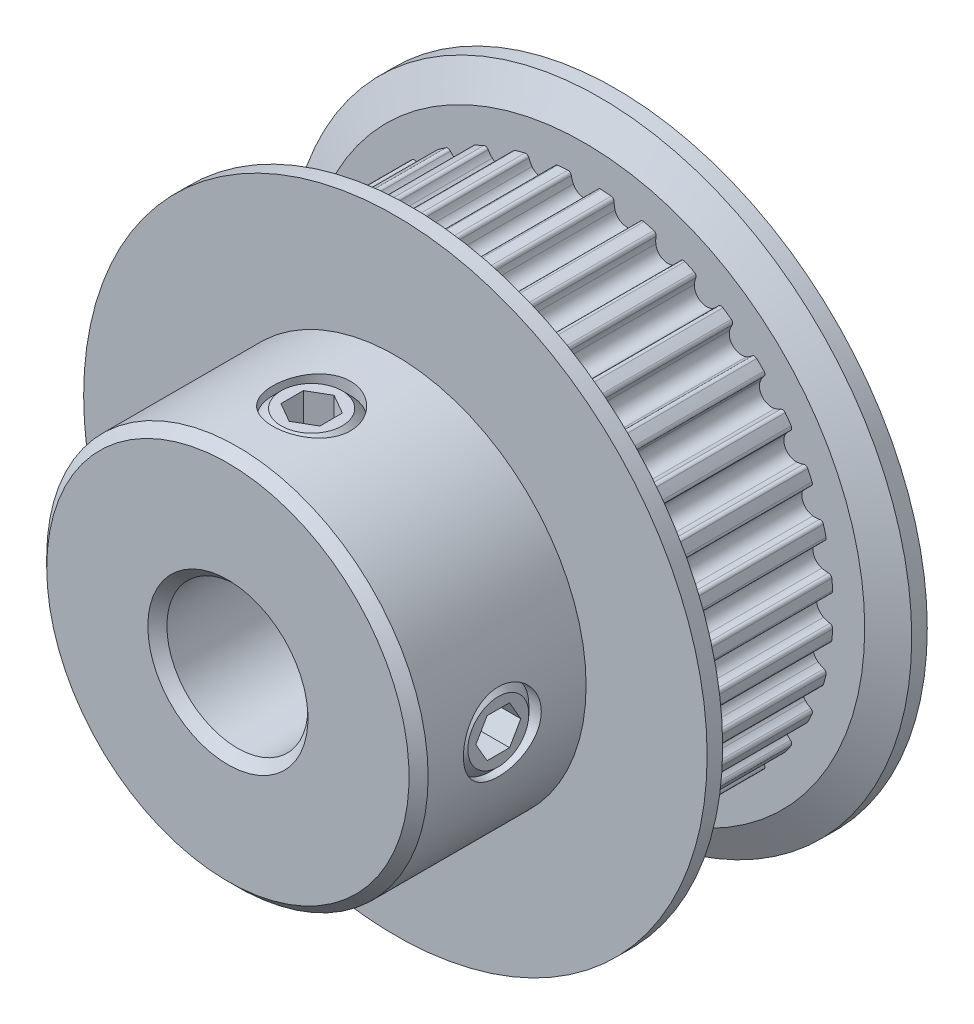
SolidWorks part; units mm, degrees
ref_plane "Front Plane" through (0, 0, 0) normal (0, 0, 1) x (1, 0, 0)
ref_plane "Top Plane" through (0, 0, 0) normal (0, 1, 0) x (1, 0, 0)
ref_plane "Right Plane" through (0, 0, 0) normal (1, 0, 0) x (0, 0, -1)
sketch "Sketch1" plane through (0, 0, 0) normal (0, 0, 1) x (1, 0, 0)
  line L1 (-1.8459, 10.4515) -> (1.8459, 10.4515) construction
  line L4 (0, 0) -> (0, 10.4515) construction
  line L5 (0, 10.4515) -> (0, 14.6059) construction
  line L6 (0, 11.4555) -> (1.9924, 11.2809) construction
  line L7 (1.9924, 11.2809) -> (2.8218, 11.1344) construction
  line L8 (1.9924, 11.2809) -> (1.8459, 10.4515) construction
  line L9 (-1.9924, 11.2809) -> (-1.8459, 10.4515) construction
  line L10 (-1.9482, 11.0308) -> (-2.4785, 14.0335)
  line L11 (-2.4785, 14.0335) -> (2.4785, 14.0335)
  line L12 (2.4785, 14.0335) -> (1.9482, 11.0308)
  circle A0 centre (0, 0) radius 11.4555 construction
  circle A1 centre (0, 0) radius 14.0335 construction
  circle A2 centre (0, 0) radius 11.2015 construction
  arc A3 (-0.4989, 10.7633) -> (0.4989, 10.7633) centre (0, 11.0065) ccw
  arc A4 (-0.4989, 10.7633) -> (-0.5884, 11.0497) centre (0.4, 11.2015) cw
  arc A5 (-1.9482, 11.0308) -> (-0.7467, 11.1766) centre (0, 0) cw
  arc A6 (-0.5884, 11.0497) -> (-0.7467, 11.1766) centre (-0.7367, 11.0269) ccw
  arc A7 (1.9482, 11.0308) -> (0.7467, 11.1766) centre (0, 0) ccw
  arc A8 (0.5884, 11.0497) -> (0.7467, 11.1766) centre (0.7367, 11.0269) cw
  arc A9 (0.4989, 10.7633) -> (0.5884, 11.0497) centre (-0.4, 11.2015) ccw
  point P6 (0, 20.9083)
  point P11 (0, 11.4555)
  point P13 (0, 14.0335)
  point P14 (0, 11.2015)
  dimension "D1" = 6.3025
  dimension "D2" = 3.1504
sketch "Sketch2" plane through (0, 0, 0) normal (1, 0, 0) x (0, 0, -1)
  line L0 (-8.7249, 3.175) -> (8.7249, 3.175)
  line L1 (-8.7249, 3.175) -> (-8.7249, 8.585)
  line L2 (-8.7249, 8.585) -> (-1.1851, 8.585)
  line L3 (-1.1851, 8.585) -> (-1.1851, 14.0335)
  line L4 (-1.1851, 14.0335) -> (0.2149, 14.0335) construction
  line L5 (0.2149, 14.0335) -> (0.2149, 11.2015) construction
  line L6 (0.2149, 11.2015) -> (7.3249, 11.2015)
  line L7 (7.3249, 11.2015) -> (7.3249, 14.0335) construction
  line L8 (7.3249, 14.0335) -> (8.7249, 14.0335) construction
  line L9 (8.7249, 14.0335) -> (8.7249, 3.175)
  line L10 (-8.7249, 0) -> (8.7249, 0) construction
  line L11 (8.0249, 14.0335) -> (7.3249, 12.6175)
  line L12 (0.2149, 12.6175) -> (-0.4851, 14.0335)
  line L13 (-1.1851, 14.0335) -> (-0.4851, 14.0335)
  line L14 (0.2149, 12.6175) -> (0.2149, 11.2015)
  line L15 (7.3249, 11.2015) -> (7.3249, 12.6175)
  line L16 (8.0249, 14.0335) -> (8.7249, 14.0335)
  arc A0 (0.2149, 12.6175) -> (-0.4851, 14.0335) centre (-1.5673, 12.6175) ccw construction
  arc A1 (7.3249, 12.6175) -> (8.0249, 14.0335) centre (9.1071, 12.6175) cw construction
  point P12 (0.2149, 12.6175)
  point P14 (-0.4851, 14.0335)
  point P20 (7.3249, 12.6175)
  point P21 (8.0249, 14.0335)
  point P25 (7.3249, 0)
  point P26 (0.2149, 0)
revolve "Revolve1" add sketch "Sketch2" angle 360 mid plane about L10
sketch "Sketch3" plane through (0, 0, 0) normal (0, 0, 1) x (1, 0, 0)
  line L6 (2.4785, 14.0335) -> (-2.4785, 14.0335)
  line L7 (1.9482, 11.0308) -> (2.4785, 14.0335)
  line L8 (-2.4785, 14.0335) -> (-1.9482, 11.0308)
  line L9 (2.4785, 14.0335) -> (-2.4785, 14.0335)
  line L10 (1.9482, 11.0308) -> (2.4785, 14.0335)
  line L11 (-2.4785, 14.0335) -> (-1.9482, 11.0308)
  arc A8 (1.9482, 11.0308) -> (0.7467, 11.1766) centre (0, 0) ccw
  arc A9 (0.7467, 11.1766) -> (0.5884, 11.0497) centre (0.7367, 11.0269) ccw
  arc A10 (0.4989, 10.7633) -> (0.5884, 11.0497) centre (-0.4, 11.2015) ccw
  arc A11 (-0.4989, 10.7633) -> (0.4989, 10.7633) centre (0, 11.0065) ccw
  arc A12 (-0.5884, 11.0497) -> (-0.4989, 10.7633) centre (0.4, 11.2015) ccw
  arc A13 (-0.5884, 11.0497) -> (-0.7467, 11.1766) centre (-0.7367, 11.0269) ccw
  arc A14 (-0.7467, 11.1766) -> (-1.9482, 11.0308) centre (0, 0) ccw
  arc A15 (1.9482, 11.0308) -> (0.7467, 11.1766) centre (0, 0) ccw
  arc A16 (0.7467, 11.1766) -> (0.5884, 11.0497) centre (0.7367, 11.0269) ccw
  arc A17 (0.4989, 10.7633) -> (0.5884, 11.0497) centre (-0.4, 11.2015) ccw
  arc A18 (-0.4989, 10.7633) -> (0.4989, 10.7633) centre (0, 11.0065) ccw
  arc A19 (-0.5884, 11.0497) -> (-0.4989, 10.7633) centre (0.4, 11.2015) ccw
  arc A20 (-0.5884, 11.0497) -> (-0.7467, 11.1766) centre (-0.7367, 11.0269) ccw
  arc A21 (-0.7467, 11.1766) -> (-1.9482, 11.0308) centre (0, 0) ccw
  dimension "D1" = 0
extrude "Cut-Extrude1" cut sketch "Sketch3" against normal up to vertex (7.3249 mm away) from vertex up to point (0, 11.2015, -7.3249) starting at point (0, 11.2015, -0.2149)
pattern_circular "CirPattern1" count 36 over 360 about axis through (0, 0, 8.7249) along (0, 0, 1) of "Cut-Extrude1"
sketch "Sketch4" plane through (0, 0, 0) normal (1, 0, 0) x (0, -1, 0)
  line L0 (0, -1.1851) -> (0, -8.7249) construction
  line L1 (-8.585, -1.1851) -> (8.585, -1.1851) construction
  line L2 (-8.585, -8.7249) -> (8.585, -8.7249) construction
  circle A0 centre (0, -4.955) radius 1.7526
extrude "Cut-Extrude2" cut sketch "Sketch4" along normal through all
ref_plane "Plane1" through (0, 0, 4.955) normal (0, 0, 1) x (1, 0, 0)
sketch "Sketch5" plane through (0, 0, 4.955) normal (0, 0, 1) x (1, 0, 0)
  line L0 (0, 0.1664) -> (0, 8.585) construction
  line L1 (3.175, -1.3716) -> (3.175, 0)
  line L2 (3.556, -1.7526) -> (8.0232, -1.7526)
  line L3 (3.175, 0) -> (8.585, 0) construction
  line L4 (3.175, 0) -> (8.4042, 0)
  line L5 (8.4042, 0) -> (8.4042, -1.3716)
  line L6 (3.556, -1.7526) -> (3.175, -1.3716)
  line L7 (8.4042, -1.3716) -> (8.0232, -1.7526)
  circle A0 centre (0, 0) radius 8.585 construction
  circle A1 centre (0, 0) radius 3.175 construction
  point P2 (3.175, -1.7526)
  point P11 (8.4042, -1.7526)
revolve "Revolve2" add sketch "Sketch5" angle 360 mid plane about L4
sketch "Sketch6" plane through (8.4042, 5.3841, 0) normal (-1, 0, 0) x (0, -1, 0)
  line L1 (5.3841, 5.9669) -> (4.5078, 5.4609)
  line L2 (4.5078, 5.4609) -> (4.5078, 4.4491)
  line L3 (4.5078, 4.4491) -> (5.3841, 3.9431)
  line L4 (5.3841, 3.9431) -> (6.2604, 4.4491)
  line L5 (6.2604, 4.4491) -> (6.2604, 5.4609)
  line L6 (6.2604, 5.4609) -> (5.3841, 5.9669)
  circle A0 centre (5.3841, 4.955) radius 0.8763 construction
  dimension "D1" = 1.7526
extrude "Cut-Extrude3" cut sketch "Sketch6" along normal blind 1.3144
pattern_circular "CirPattern2" count 2 over 90 about axis through (0, 0, 8.7249) along (0, 0, 1) of "Cut-Extrude2", "Revolve2", "Cut-Extrude3"
chamfer "Chamfer1" distance 0.4293 angle 45 2 edges at (3.175, 0, 8.7249) (8.585, 0, 8.7249)
ref_axis "Center Axis 1" through (0, 0, -8.7249) along (0, 0, 1)
ref_plane "Contact Plane 1" through (0, 0, 8.7249) normal (0, 0, 1) x (1, 0, 0)
ref_plane "Contact Plane 2" through (0, 0, -8.7249) normal (0, 0, -1) x (-1, 0, 0)
equation "\"D2@Sketch1\" = \"D1@Sketch1\"/2"
equation "\"D1@Sketch6\" = \"Set Screw@Sketch4\" / 2"
equation "\"D1@Cut-Extrude3\" = \"D1@Sketch6\"*.75"
equation "\"D1@Chamfer1\"=\"Hub Dia@Sketch2\"*.025"
